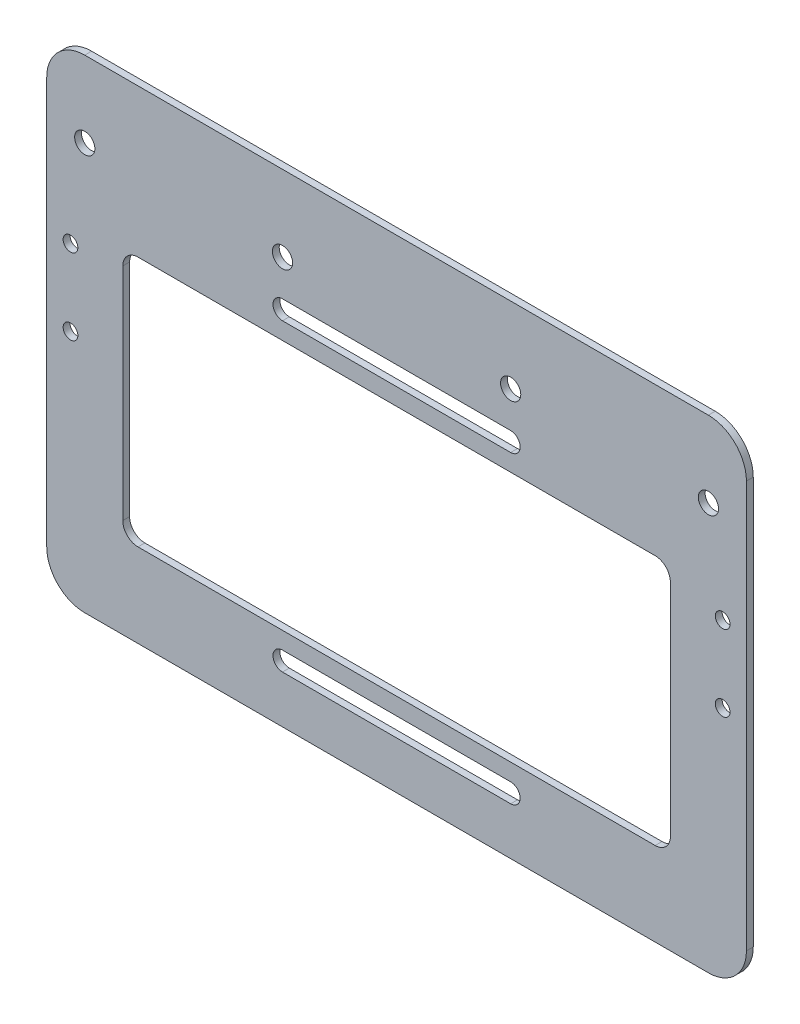
SolidWorks part; units mm, degrees
ref_plane "Front Plane" through (0, 0, 0) normal (0, 0, 1) x (1, 0, 0)
ref_plane "Top Plane" through (0, 0, 0) normal (0, 1, 0) x (1, 0, 0)
ref_plane "Right Plane" through (0, 0, 0) normal (1, 0, 0) x (0, 0, -1)
sketch "Sketch1" plane through (0, 0, 0) normal (0, 0, 1) x (1, 0, 0)
  line L1 (-116.84, 80.645) -> (116.84, 80.645)
  line L2 (-116.84, 80.645) -> (-116.84, -80.645)
  line L3 (-116.84, -80.645) -> (116.84, -80.645)
  line L4 (116.84, 80.645) -> (116.84, -80.645)
  line L5 (-116.84, 80.645) -> (116.84, -80.645) construction
  line L6 (-116.84, -80.645) -> (116.84, 80.645) construction
  line L7 (-86.36, 31.115) -> (86.36, 31.115)
  line L8 (-91.44, 26.035) -> (-91.44, -47.625)
  line L9 (-86.36, -52.705) -> (86.36, -52.705)
  line L10 (91.44, 26.035) -> (91.44, -47.625)
  line L11 (-91.44, 31.115) -> (91.44, -52.705) construction
  line L12 (-91.44, -52.705) -> (91.44, 31.115) construction
  arc A0 (86.36, -52.705) -> (91.44, -47.625) centre (86.36, -47.625) ccw
  arc A1 (86.36, 31.115) -> (91.44, 26.035) centre (86.36, 26.035) cw
  arc A2 (-91.44, 26.035) -> (-86.36, 31.115) centre (-86.36, 26.035) cw
  arc A3 (-86.36, -52.705) -> (-91.44, -47.625) centre (-86.36, -47.625) cw
  point P0 (0, 0)
  point P5 (0, -10.795)
  dimension "D7" = 5.08
  dimension "D1" = 25.4
  dimension "D2" = 161.29
  dimension "D3" = 182.88
  dimension "D4" = 83.82
  dimension "D5" = 27.94
  dimension "D6" = 233.68
extrude "Boss-Extrude1" add sketch "Sketch1" along normal blind 2.286
sketch "Sketch2" plane through (0, 0, 2.286) normal (0, 0, 1) x (1, 0, 0)
  line L0 (38.1, 40.005) -> (-38.1, 40.005) construction
  line L1 (38.1, 36.83) -> (-38.1, 36.83)
  line L2 (38.1, 43.18) -> (-38.1, 43.18)
  line L3 (-91.44, 26.035) -> (-91.44, -47.625) construction
  line L4 (-91.44, -10.795) -> (91.44, -10.795) construction
  line L5 (-91.44, 26.035) -> (-91.44, -47.625) construction
  line L6 (91.44, -47.625) -> (91.44, 26.035) construction
  line L7 (38.1, -61.595) -> (-38.1, -61.595) construction
  line L8 (38.1, -58.42) -> (-38.1, -58.42)
  line L9 (38.1, -64.77) -> (-38.1, -64.77)
  arc A0 (38.1, 36.83) -> (38.1, 43.18) centre (38.1, 40.005) ccw
  arc A1 (-38.1, 43.18) -> (-38.1, 36.83) centre (-38.1, 40.005) ccw
  arc A2 (38.1, -58.42) -> (38.1, -64.77) centre (38.1, -61.595) cw
  arc A3 (-38.1, -64.77) -> (-38.1, -58.42) centre (-38.1, -61.595) cw
  point P2 (0, 40.005)
  point P7 (-91.44, -10.795)
  point P19 (0, -61.595)
  dimension "D1" = 76.2
  dimension "D2" = 50.8
  dimension "D3" = 6.35
extrude "Cut-Extrude1" cut sketch "Sketch2" against normal through all
hole_wizard "1/4 Clearance Hole1" positions "Sketch4" profile "Sketch3" hole size "1/4" standard "ANSI Inch" end condition through all
sketch "Sketch4" plane through (0, 0, 2.286) normal (0, 0, 1) x (1, 0, 0)
  line L2 (116.84, 80.645) -> (-116.84, 80.645) construction
  line L3 (-38.1, 55.245) -> (38.1, 55.245) construction
  point P0 (-38.1, 55.245)
  point P8 (38.1, 55.245)
  point P22 (0, 55.245)
  dimension "D1" = 76.2
  dimension "D3" = 25.4
sketch "Sketch3" plane through (-38.1, 55.245, 2.286) normal (1, 0, 0) x (0, -1, 0)
  line L0 (0, 0) -> (0, 2.286)
  line L1 (0, 2.286) -> (3.3782, 2.286)
  line L2 (3.3782, 2.286) -> (3.3782, 0)
  line L5 (3.3782, 0) -> (0, 0)
  line L11 (0, -6.35) -> (0, 107.95) construction
  dimension "Thru Hole Dia." = 6.7564
  dimension "Thru Hole Depth" = 2.286
hole_wizard "1/4 Clearance Hole2" positions "Sketch8" profile "Sketch7" hole size "1/4" standard "ANSI Inch" end condition through all
sketch "Sketch8" plane through (0, 0, 2.286) normal (0, 0, 1) x (1, 0, 0)
  line L0 (-116.84, 80.645) -> (-116.84, -80.645) construction
  line L1 (116.84, -80.645) -> (116.84, 80.645) construction
  line L2 (116.84, 80.645) -> (-116.84, 80.645) construction
  point P0 (-104.14, 55.245)
  point P2 (104.14, 55.245)
  dimension "D1" = 12.7
  dimension "D2" = 12.7
  dimension "D3" = 25.4
sketch "Sketch7" plane through (-104.14, 55.245, 2.286) normal (1, 0, 0) x (0, -1, 0)
  line L0 (0, 0) -> (0, 2.286)
  line L1 (0, 2.286) -> (3.3782, 2.286)
  line L2 (3.3782, 2.286) -> (3.3782, 0)
  line L5 (3.3782, 0) -> (0, 0)
  line L11 (0, -6.35) -> (0, 107.95) construction
  dimension "Thru Hole Dia." = 6.7564
  dimension "Thru Hole Depth" = 2.286
hole_wizard "#10 (0.1935) Diameter Hole1" positions "Sketch10" profile "Sketch9" hole size "#10" standard "ANSI Inch" end condition through all
sketch "Sketch10" plane through (0, 0, 2.286) normal (0, 0, 1) x (1, 0, 0)
  line L2 (-116.84, 80.645) -> (-116.84, -80.645) construction
  line L3 (-108.9025, -1.651) -> (-108.9025, 23.749) construction
  line L6 (-115.2525, 30.099) -> (-102.5525, 30.099) construction
  line L7 (-115.2525, 30.099) -> (-115.2525, -8.001) construction
  line L9 (-102.5525, 30.099) -> (-102.5525, -8.001) construction
  line L10 (-115.2525, 30.099) -> (-102.5525, -8.001) construction
  line L11 (-115.2525, -8.001) -> (-102.5525, 30.099) construction
  point P0 (-108.9025, 23.749)
  point P2 (-108.9025, -1.651)
  dimension "D1" = 25.4
  dimension "D3" = 7.9375
  dimension "D4" = 38.1
  dimension "D5" = 12.7
sketch "Sketch9" plane through (-108.9025, 23.749, 2.286) normal (1, 0, 0) x (0, -1, 0)
  line L0 (0, 0) -> (0, 2.286)
  line L1 (0, 2.286) -> (2.4574, 2.286)
  line L2 (2.4574, 2.286) -> (2.4574, 0)
  line L5 (2.4574, 0) -> (0, 0)
  line L11 (0, -6.35) -> (0, 107.95) construction
  dimension "Thru Hole Dia." = 4.9149
  dimension "Thru Hole Depth" = 2.286
mirror "Mirror1" about plane through (0, 0, 0) normal (1, 0, 0) of "#10 (0.1935) Diameter Hole1"
fillet "Fillet1" radius 12.7 4 edges at (-116.84, 80.645, 1.143) (116.84, 80.645, 1.143) (-116.84, -80.645, 1.143) (116.84, -80.645, 1.143)
